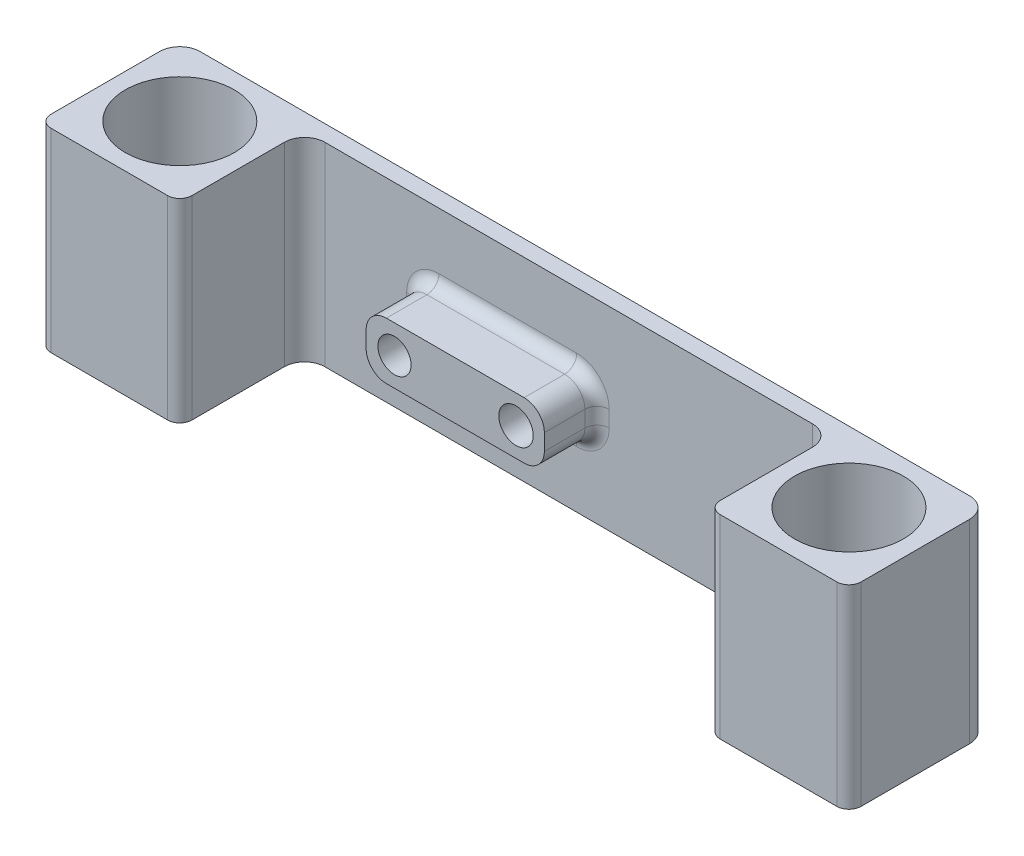
SolidWorks part; units mm, degrees
ref_plane "Front Plane" through (0, 0, 0) normal (0, 0, 1) x (1, 0, 0)
ref_plane "Top Plane" through (0, 0, 0) normal (0, 1, 0) x (1, 0, 0)
ref_plane "Right Plane" through (0, 0, 0) normal (1, 0, 0) x (0, 0, -1)
sketch "Sketch1" plane through (0, 0, 0) normal (0, 1, 0) x (1, 0, 0)
  line L1 (-17.4, 17.4) -> (17.4, 17.4)
  line L2 (-17.4, 13.4) -> (-17.4, -17.4)
  line L3 (-17.4, -17.4) -> (17.4, -17.4)
  line L4 (17.4, 17.4) -> (17.4, -17.4)
  line L5 (0, -17.4) -> (0, 17.4) construction
  line L6 (-17.4, 0) -> (17.4, 0) construction
  line L7 (-17.4, 17.4) -> (-82.6, 17.4)
  line L9 (-17.4, 13.4) -> (-82.6, 13.4)
  line L10 (-82.6, 17.4) -> (-82.6, 13.4)
  circle A0 centre (0, 0) radius 13.45
  dimension "D1" = 26.9
  dimension "D2" = 34.8
  dimension "D3" = 34.8
  dimension "D4" = 65.2
  dimension "D5" = 4
extrude "Boss-Extrude2" add sketch "Sketch1" along normal blind 48
mirror "Mirror2" about plane through (-82.6, 48, -17.4) normal (1, 0, 0) of "Boss-Extrude2"
sketch "Sketch7" plane through (0, 0, -13.4) normal (0, 0, 1) x (1, 0, 0)
  line L0 (-147.8, 24) -> (-17.4, 24) construction
  line L1 (-147.8, 48) -> (-147.8, 0) construction
  line L2 (-17.4, 48) -> (-17.4, 0) construction
  line L3 (-82.6, 48) -> (-82.6, 0) construction
  line L4 (-147.8, 48) -> (-17.4, 48) construction
  line L5 (-147.8, 0) -> (-17.4, 0) construction
  line L6 (-112.6, 24) -> (-82.6, 24) construction
  line L8 (-119.6, 17) -> (-75.6, 17)
  line L9 (-119.6, 17) -> (-119.6, 31)
  line L10 (-119.6, 31) -> (-75.6, 31)
  line L11 (-75.6, 17) -> (-75.6, 31)
  line L12 (-97.6, 31) -> (-97.6, 17) construction
  line L13 (-119.6, 24) -> (-75.6, 24) construction
  circle A0 centre (-82.6, 24) radius 4.25
  circle A2 centre (-112.6, 24) radius 4.1
  point P15 (-97.6, 24)
  dimension "D1" = 8.5
  dimension "D3" = 8.2
  dimension "D5" = 30
  dimension "D2" = 14
  dimension "D4" = 44
extrude "Boss-Extrude3" add sketch "Sketch7" along normal blind 13
fillet "Fillet1" radius 3 4 edges at (17.4, 24, 17.4) (-17.4, 24, 17.4) (-182.6, 24, 17.4) (-147.8, 24, 17.4)
fillet "Fillet2" radius 5 4 edges at (17.4, 24, -17.4) (-17.4, 24, -13.4) (-182.6, 24, -17.4) (-147.8, 24, -13.4)
fillet "Fillet3" radius 5 4 edges at (-75.6, 31, -6.9) (-75.6, 17, -6.9) (-119.6, 31, -6.9) (-119.6, 17, -6.9)
fillet "Fillet4" radius 3 8 edges at (-118.1355, 18.4645, -13.4) (-119.6, 24, -13.4) (-118.1355, 29.5355, -13.4) (-97.6, 31, -13.4) (-77.0645, 29.5355, -13.4) (-75.6, 24, -13.4) (-77.0645, 18.4645, -13.4) (-97.6, 17, -13.4)
